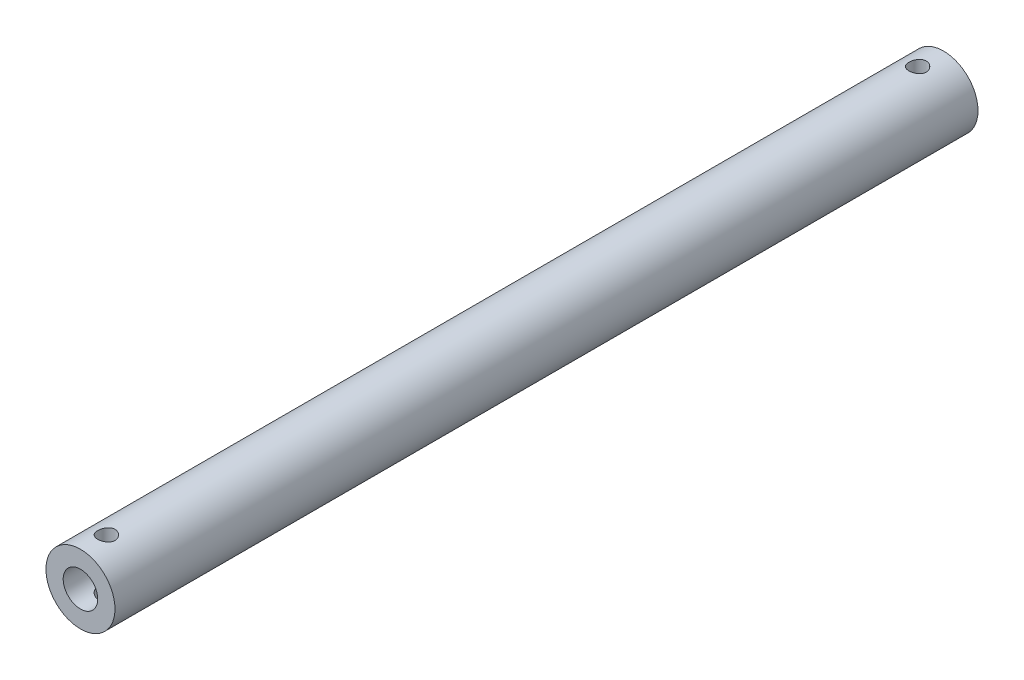
SolidWorks part; units mm, degrees
ref_plane "Plan de face" through (0, 0, 0) normal (0, 0, 1) x (1, 0, 0)
ref_plane "Plan de dessus" through (0, 0, 0) normal (0, 1, 0) x (1, 0, 0)
ref_plane "Plan de droite" through (0, 0, 0) normal (1, 0, 0) x (0, 0, -1)
sketch "Esquisse1" plane through (0, 0, 0) normal (0, 0, 1) x (1, 0, 0)
  circle A0 centre (-4.9182, 1.1045) radius 4
  circle A1 centre (-4.9182, 1.1045) radius 2
  dimension "D1" = 4
  dimension "D2" = 8
extrude "Boss.-Extru.1" add sketch "Esquisse1" along normal blind 100
ref_plane "Plan1" through (0, 5.1045, 0) normal (0, 1, 0) x (1, 0, 0)
sketch "Esquisse2" plane through (0, 5.1045, 0) normal (0, 1, 0) x (1, 0, 0)
  line L0 (-4.9182, 0) -> (-4.9182, -100) construction
  line L1 (-0.9182, 0) -> (-8.9182, 0) construction
  line L2 (-8.9182, -100) -> (-0.9182, -100) construction
  circle A0 centre (-4.9182, -3) radius 1
  circle A1 centre (-4.9182, -97) radius 1
  dimension "D2" = 2
  dimension "D3" = 2
  dimension "D1" = 3
  dimension "D4" = 3
extrude "Enlèv. mat.-Extru.1" cut sketch "Esquisse2" against normal through all
